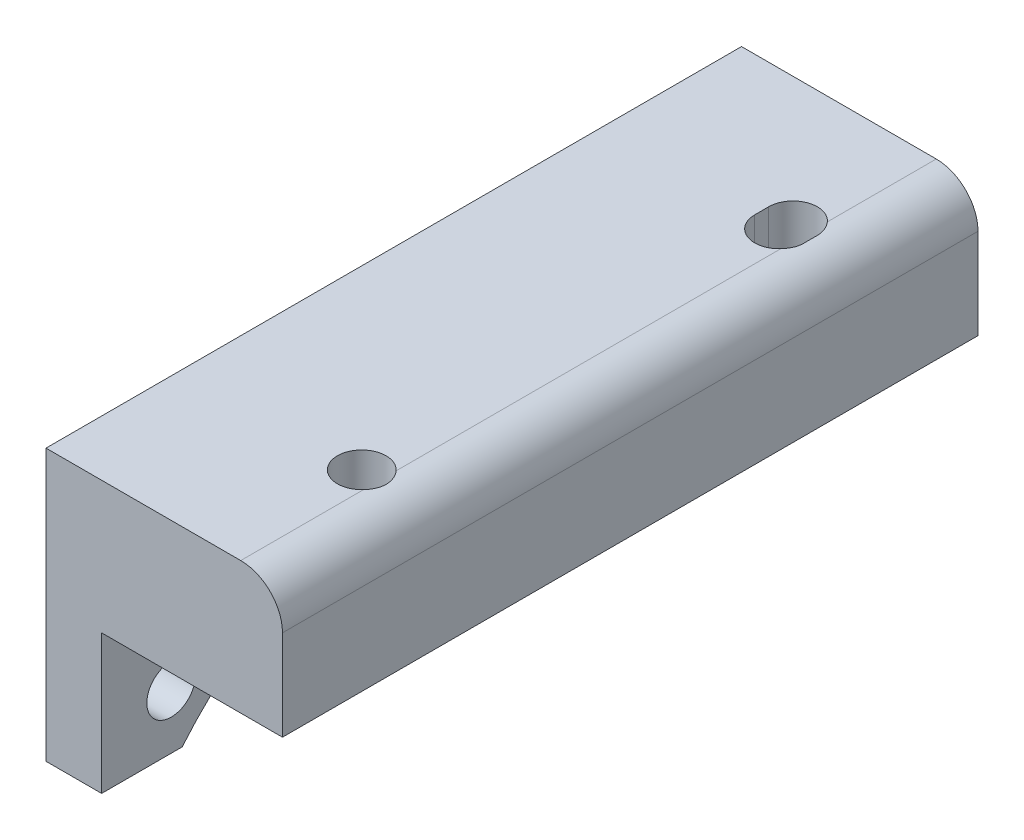
SolidWorks part; units mm, degrees
ref_plane "Plan de face" through (0, 0, 0) normal (0, 0, 1) x (1, 0, 0)
ref_plane "Plan de dessus" through (0, 0, 0) normal (0, 1, 0) x (1, 0, 0)
ref_plane "Plan de droite" through (0, 0, 0) normal (1, 0, 0) x (0, 0, -1)
sketch "Esquisse1" plane through (0, 0, 0) normal (0, 0, 1) x (1, 0, 0)
  line L1 (0, 0) -> (13, 0)
  line L2 (0, 0) -> (0, 9.5)
  line L3 (0, 9.5) -> (13, 9.5)
  line L4 (13, 0) -> (13, 9.5)
  dimension "D1" = 9.5
  dimension "D2" = 13
extrude "Boss.-Extru.1" add sketch "Esquisse1" along normal blind 50
sketch "Esquisse2" plane through (0, 9.5, 0) normal (0, 1, 0) x (1, 0, 0)
  line L0 (13, -50) -> (0, -50) construction
  line L2 (13, -50) -> (13, 0) construction
  line L3 (8.7, -10) -> (8.7, -9) construction
  line L4 (6.95, -10) -> (6.95, -9)
  line L5 (10.45, -10) -> (10.45, -9)
  circle A0 centre (8.7, -40) radius 1.75
  arc A2 (6.95, -10) -> (10.45, -10) centre (8.7, -10) ccw
  arc A3 (10.45, -9) -> (6.95, -9) centre (8.7, -9) ccw
  point P6 (8.7, -9.5)
  dimension "D3" = 3.5
  dimension "D1" = 40
  dimension "D2" = 10
  dimension "D5" = 4.3
  dimension "D6" = 4.3
  dimension "D7" = 3.5
  dimension "D8" = 1
extrude "Enlèv. mat.-Extru.1" cut sketch "Esquisse2" against normal blind 500
sketch "Esquisse3" plane through (0, 0, 0) normal (-1, 0, 0) x (0, 0, 1)
  line L0 (50, 9.5) -> (50, 0) construction
  line L1 (0, 9.5) -> (50, 9.5)
  line L2 (0, 9.5) -> (0, -52)
  line L3 (0, -52) -> (50, -52)
  line L4 (50, 9.5) -> (50, -52)
  line L5 (50, 0) -> (0, 0) construction
  dimension "D1" = 52
extrude "Boss.-Extru.2" add sketch "Esquisse3" along normal blind 4
sketch "Esquisse4" plane through (0, 0, 0) normal (1, 0, 0) x (0, 0, -1)
  line L0 (-50, -26) -> (0, -26) construction
  line L1 (-50, -52) -> (-50, 0) construction
  line L2 (0, 0) -> (0, -52) construction
  line L3 (-50, -10) -> (-44.2094, -10)
  line L4 (-44.2094, -10) -> (-5.7906, -10) construction
  line L5 (-5.7906, -10) -> (0, -10)
  line L6 (-50, 0) -> (0, 0) construction
  line L7 (-45, -6) -> (-5, -6) construction
  circle A0 centre (-25, -26) radius 25
  circle A1 centre (-45, -6) radius 1.75
  circle A2 centre (-5, -6) radius 1.75
  point P9 (-25, -26)
  point P19 (-25, -6)
  line M3 (-50, 0) -> (-50, -52)
  line M4 (-50, -52) -> (0, -52)
  line M5 (0, -52) -> (0, 0)
  dimension "D1" = 50
  dimension "D3" = 3.5
  dimension "D4" = 3.5
  dimension "D2" = 10
  dimension "D5" = 40
  dimension "D6" = 20
extrude "Enlèv. mat.-Extru.2" cut sketch "Esquisse4" against normal blind 33.5 contours A0 | A0 L3 M3 | A0 M4 M5 | A0 L5 M5 | A1 | A2 region at (0, -13.9014, 48.3037) region at (0, -26, 25) region at (0, -51.5636, 25) region at (0, -13.9014, 1.6963) region at (0, -6, 45) region at (0, -6, 5)
fillet "Congé2" radius 3 1 edges at (13, 9.5, 25)
sketch "Esquisse5" plane through (0, 0, 0) normal (0, -1, 0) x (-1, 0, 0)
  line L0 (-13, -50) -> (-13, 0) construction
  line L1 (-11.6, -38.3257) -> (-11.6, -41.6743)
  line L2 (-11.6, -41.6743) -> (-8.7, -43.3486)
  line L3 (-8.7, -43.3486) -> (-5.8, -41.6743)
  line L4 (-5.8, -41.6743) -> (-5.8, -38.3257)
  line L5 (-5.8, -38.3257) -> (-8.7, -36.6514)
  line L6 (-8.7, -36.6514) -> (-11.6, -38.3257)
  line L7 (-11.6, -11.6743) -> (-8.7, -13.3486)
  line L8 (-8.7, -13.3486) -> (-5.8, -11.6743)
  line L9 (-5.8, -11.6743) -> (-5.8, -8.3257)
  line L10 (-5.8, -8.3257) -> (-8.7, -6.6514)
  line L11 (-8.7, -6.6514) -> (-11.6, -8.3257)
  line L12 (-11.6, -8.3257) -> (-11.6, -11.6743)
  line L14 (-11.6, -7.3257) -> (-11.6, -10.6743)
  line L15 (-11.6, -10.6743) -> (-8.7, -12.3486)
  line L16 (-8.7, -12.3486) -> (-5.8, -10.6743)
  line L17 (-5.8, -10.6743) -> (-5.8, -7.3257)
  line L18 (-5.8, -7.3257) -> (-8.7, -5.6514)
  line L19 (-8.7, -5.6514) -> (-11.6, -7.3257)
  circle A0 centre (-8.7, -40) radius 2.9 construction
  circle A1 centre (-8.7, -10) radius 2.9 construction
  circle A2 centre (-8.7, -9) radius 2.9 construction
  line M7 (-6.95, -9) -> (-6.95, -10)
  arc M8 (-6.95, -10) -> (-10.45, -10) centre (-8.7, -10) cw
  line M9 (-10.45, -10) -> (-10.45, -9)
  arc M10 (-10.45, -9) -> (-6.95, -9) centre (-8.7, -9) cw
  circle M11 centre (-8.7, -40) radius 1.75
  dimension "D1" = 5.8
  dimension "D2" = 5.8
  dimension "D3" = 5.8
extrude "Enlèv. mat.-Extru.3" cut sketch "Esquisse5" against normal blind 5 contours L5 L6 L1 L2 L3 L4 M11 | L18 L19 L14 L11 L10 L17 | L16 L15 L12 L7 L8 L9 | L15 L16 L9 L10 L11 L12 M10 M7 M8 M9 region at (10.1057, 0, 37.5653) region at (11.5361, 0, 11.1743) region at (11.5187, 0, 9.5) region at (11.5361, 0, 7.8257)
